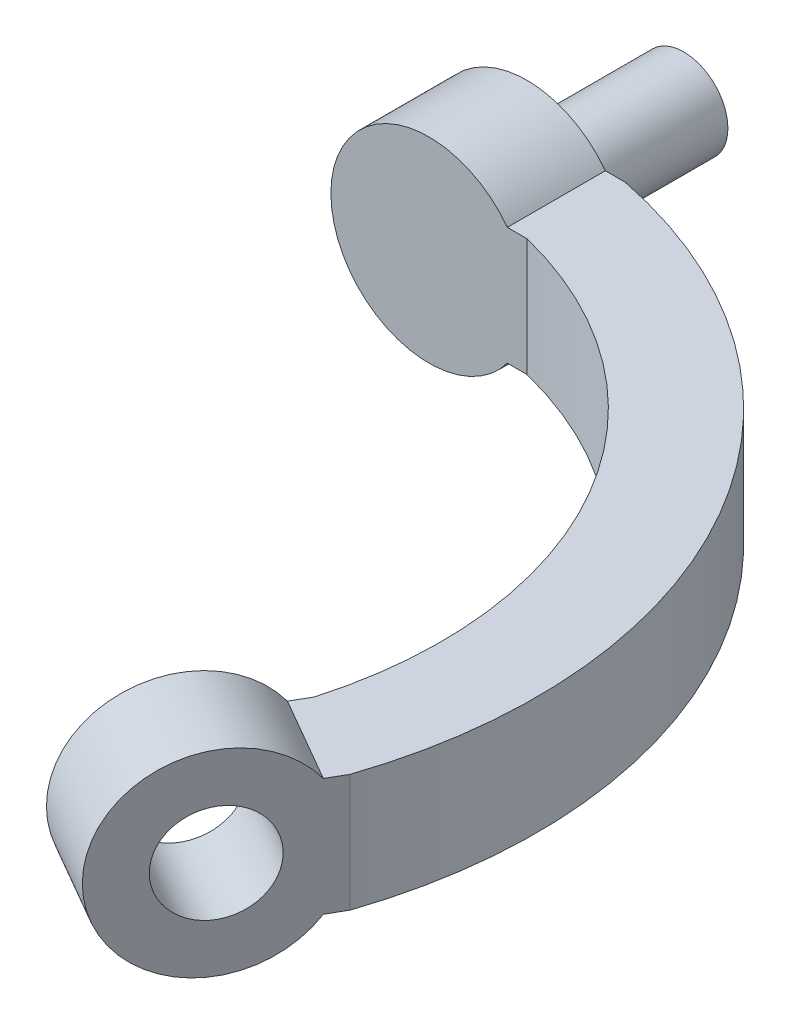
SolidWorks part; units mm, degrees
ref_plane "前视基准面" through (0, 0, 0) normal (0, 0, 1) x (1, 0, 0)
ref_plane "上视基准面" through (0, 0, 0) normal (0, 1, 0) x (1, 0, 0)
ref_plane "右视基准面" through (0, 0, 0) normal (1, 0, 0) x (0, 0, -1)
other "Configuration Table"
sketch "草图2" plane through (0, 0, 0) normal (0, 0, 1) x (1, 0, 0)
  circle A0 centre (0, 0) radius 5
  dimension "D1" = 10
extrude "凸台-拉伸3" add sketch "草图2" along normal blind 5
sketch "草图3" plane through (0, 0, 0) normal (0, 1, 0) x (1, 0, 0)
  line L0 (0, 0) -> (0, -25) construction
  line L1 (0, -25) -> (20.1468, -36.6318) construction
  line L2 (19.8205, -30.6699) -> (24.1506, -33.1699)
  line L3 (0, 0) -> (5, 0)
  line L4 (0, 0) -> (0, -5)
  line L5 (0, -5) -> (5, -5)
  line L6 (5, 0) -> (5, -5)
  line L15 (24.1506, -33.1699) -> (21.6506, -37.5)
  line L16 (21.6506, -37.5) -> (17.3205, -35)
  line L17 (17.3205, -35) -> (19.8205, -30.6699)
  arc A0 (5, -5) -> (19.8205, -30.6699) centre (0, -25) cw
  arc A1 (5, 0) -> (24.1506, -33.1699) centre (0, -25) cw
  dimension "D4" = 20
  dimension "D1" = 120
  dimension "D2" = 5
  dimension "D3" = 5
  dimension "D5" = 5
extrude "凸台-拉伸4" add sketch "草图3" along normal blind 3 and the other way blind 3 separate body contours A1 L6 A0 L2 region at (18.1912, 0, 14.4973)
revolve "旋转1" add sketch "草图3<3>" angle 360 about L1 region at (20.7356, 0, 34.0849)
sketch "草图3<3>" plane through (0, 0, 0) normal (0, 1, 0) x (1, 0, 0) same geometry as "草图3"
sketch "草图4" plane through (-8.3253, 0, 14.4199) normal (-0.5, 0, 0.866) x (0.866, 0, 0.5)
  line L4 (37.5, 3) -> (32.5, 3)
  line L5 (32.5, 3) -> (32.5, -3)
  line L6 (32.5, -3) -> (37.5, -3)
  line L7 (37.5, -3) -> (37.5, 3)
  line L8 (37.5, 3) -> (32.5, 3)
  line L9 (32.5, 3) -> (32.5, -3)
  line L10 (32.5, -3) -> (37.5, -3)
  line L11 (37.5, -3) -> (37.5, 3)
  dimension "D1" = 0
extrude "凸台-拉伸5" add sketch "草图4" along normal blind 3
sketch "草图5" plane through (5, 0, 0) normal (-1, 0, 0) x (0, 0, 1)
  line L4 (5, -3) -> (5, 3)
  line L5 (5, 3) -> (0, 3)
  line L6 (0, 3) -> (0, -3)
  line L7 (0, -3) -> (5, -3)
  line L8 (5, -3) -> (5, 3)
  line L9 (5, 3) -> (0, 3)
  line L10 (0, 3) -> (0, -3)
  line L11 (0, -3) -> (5, -3)
  dimension "D1" = 0
extrude "凸台-拉伸6" add sketch "草图5" along normal blind 3
sketch "草图6" plane through (28.1458, 0, 16.25) normal (-0.866, 0, -0.5) x (-0.5, 0, 0.866)
  circle A0 centre (21.6506, 0) radius 2.5
  dimension "D1" = 5
extrude "切除-拉伸1" cut sketch "草图6" against normal blind 5
sketch "草图7" plane through (0, 0, 5) normal (0, 0, 1) x (1, 0, 0)
  circle A0 centre (0, 0) radius 2.25
  dimension "D1" = 4.5
extrude "凸台-拉伸7" add sketch "草图7" against normal blind 8 from surface starting at face at (2.25, 0, 0)
